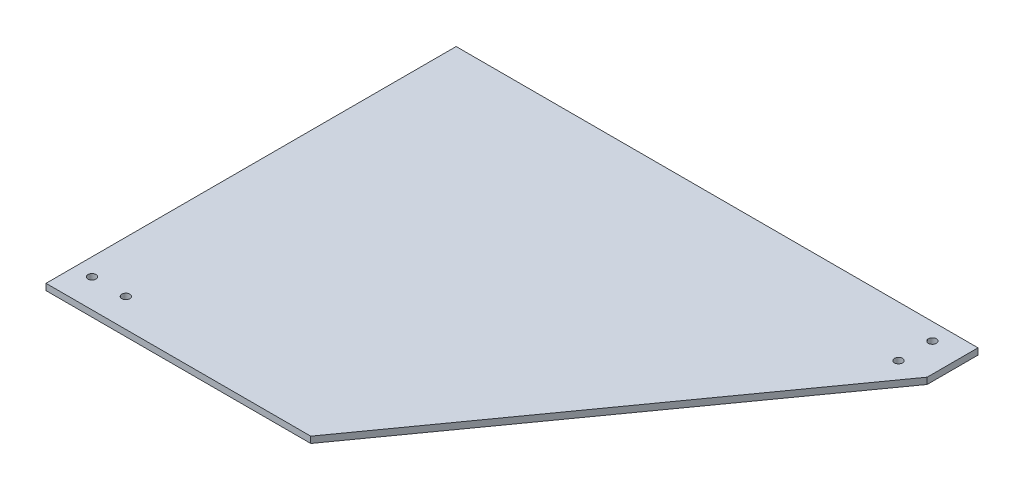
SolidWorks part; units mm, degrees
ref_plane "Front" through (0, 0, 0) normal (0, 0, 1) x (1, 0, 0)
ref_plane "Top" through (0, 0, 0) normal (0, 1, 0) x (1, 0, 0)
ref_plane "Right" through (0, 0, 0) normal (1, 0, 0) x (0, 0, -1)
ref_axis "side-side" through (80.9, 0, 0) along (-1, 0, 0)
ref_axis "up-down" through (0, 50, 0) along (0, -1, 0)
ref_axis "front-back" through (0, 0, -80.9) along (0, 0, 1)
sketch "Sketch1" plane through (0, 0, 0) normal (0, 1, 0) x (1, 0, 0)
  line L0 (0, 0) -> (0, -40.132) construction
  line L1 (-123.2, 0) -> (123.2, 0)
  line L2 (-123.2, 0) -> (-123.2, -193.652)
  line L3 (-123.2, -193.652) -> (1.8, -193.652)
  line L4 (123.2, 0) -> (123.2, -24)
  line L5 (1.8, -193.652) -> (123.2, -24)
  circle A0 centre (-99, -180.152) radius 1.8923
  circle A1 centre (109.675, -8) radius 1.8923
  circle A2 centre (-115, -180.152) radius 1.8923
  circle A3 centre (109.675, -24) radius 1.8923
  circle A5 centre (-115, -180.152) radius 1.85 construction
  circle A6 centre (-99, -180.152) radius 1.85 construction
  circle A7 centre (109.675, -8) radius 1.85 construction
  circle A8 centre (109.675, -24) radius 1.85 construction
  dimension "D3" = 24
  dimension "D7" = 3.7846
  dimension "D1" = 246.4
  dimension "D2" = 193.652
  dimension "D4" = 125
extrude "Boss-Extrude1" add sketch "Sketch1" along normal blind 3
